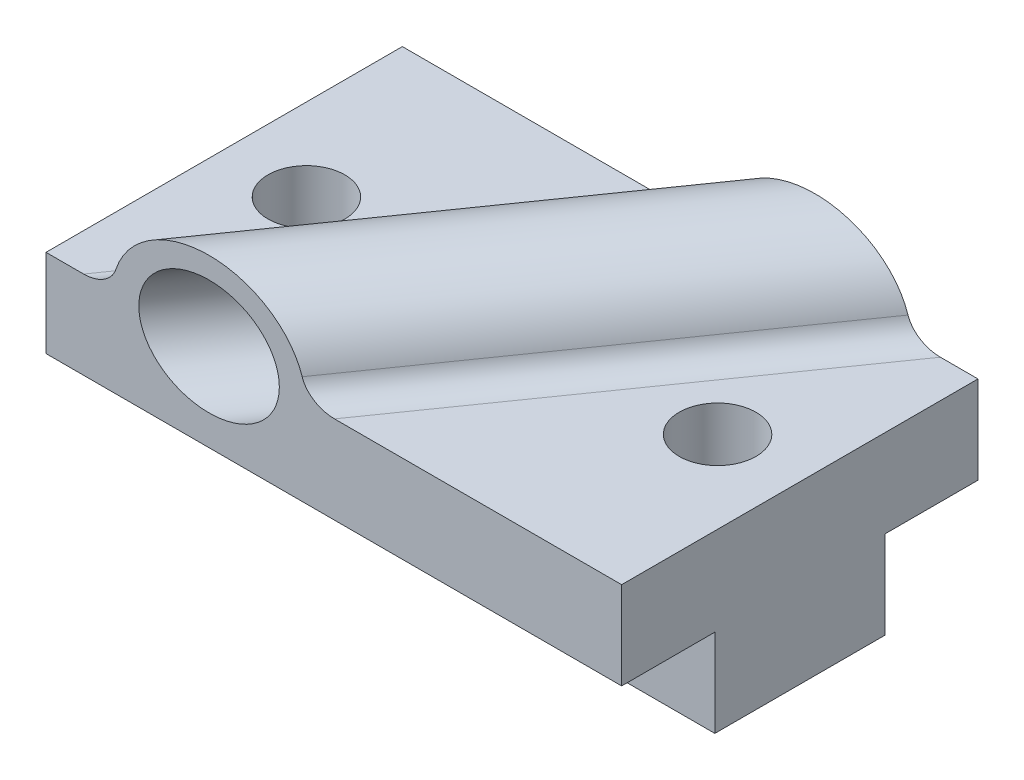
SolidWorks part; units mm, degrees
ref_plane "Front Plane" through (0, 0, 0) normal (0, 0, 1) x (1, 0, 0)
ref_plane "Top Plane" through (0, 0, 0) normal (0, 1, 0) x (1, 0, 0)
ref_plane "Right Plane" through (0, 0, 0) normal (1, 0, 0) x (0, 0, -1)
sketch "Sketch1" plane through (0, 0, 0) normal (1, 0, 0) x (0, 0, -1)
  line L0 (-32.5, 0) -> (32.5, 0)
  line L1 (32.5, 0) -> (32.5, -16)
  line L2 (32.5, -16) -> (15.5, -16)
  line L3 (15.5, -16) -> (15.5, -32)
  line L4 (15.5, -32) -> (-15.5, -32)
  line L5 (-15.5, -32) -> (-15.5, -16)
  line L6 (-15.5, -16) -> (-32.5, -16)
  line L7 (-32.5, -16) -> (-32.5, 0)
  point P0 (0, -32)
  point P4 (0, 0)
  dimension "D1" = 65
  dimension "D2" = 31
  dimension "D3" = 16
  dimension "D4" = 16
  dimension "D5" = 16
extrude "Boss-Extrude1" add sketch "Sketch1" along normal mid plane 105
sketch "Sketch2" plane through (0, 0, 0) normal (0, 1, 0) x (1, 0, 0)
  circle A0 centre (37.5, 0) radius 7
  circle A1 centre (-37.5, 0) radius 7
  dimension "D1" = 14
  dimension "D2" = 14
  dimension "D3" = 75
  dimension "D4" = 37.5
extrude "Cut-Extrude1" cut sketch "Sketch2" against normal blind 105
sketch "Sketch4" plane through (0, 0, 0) normal (0, 1, 0) x (1, 0, 0)
  line L0 (-24.5795, 0) -> (24.5795, 0) construction
  line L1 (-32.515, 22.7673) -> (32.515, -22.7673) construction
  point P0 (0, 0)
  point P4 (0, 0)
  point P8 (0, 0)
  dimension "D1" = 35
ref_plane "Plane1" through (0, 0, 0) normal (-0.5736, 0, 0.8192) x (0.8192, 0, 0.5736)
sketch "Sketch5" plane through (0, 0, 0) normal (-0.5736, 0, 0.8192) x (0.8192, 0, 0.5736)
  circle A0 centre (0, 0) radius 14.3978
extrude "Boss-Extrude2" add sketch "Sketch5" along normal up to surface (29.5937 mm away) up to face at (0, -8, 32.5)
extrude "Boss-Extrude3" add sketch "Sketch5<2>" against normal up to surface (49.7566 mm away) up to face at (0, -8, -32.5)
sketch "Sketch5<2>" plane through (0, 0, 0) normal (-0.5736, 0, 0.8192) x (0.8192, 0, 0.5736) same geometry as "Sketch5"
sketch "Sketch7" plane through (0, 0, 0) normal (-0.5736, 0, 0.8192) x (0.8192, 0, 0.5736)
  circle A0 centre (0, 0) radius 10.5
  dimension "D1" = 21
extrude "Cut-Extrude2" cut sketch "Sketch7" against normal blind 116 and the other way blind 75
fillet "Fillet1" radius 5 2 edges at (-17.5764, 0, 0) (17.5764, 0, 0)
